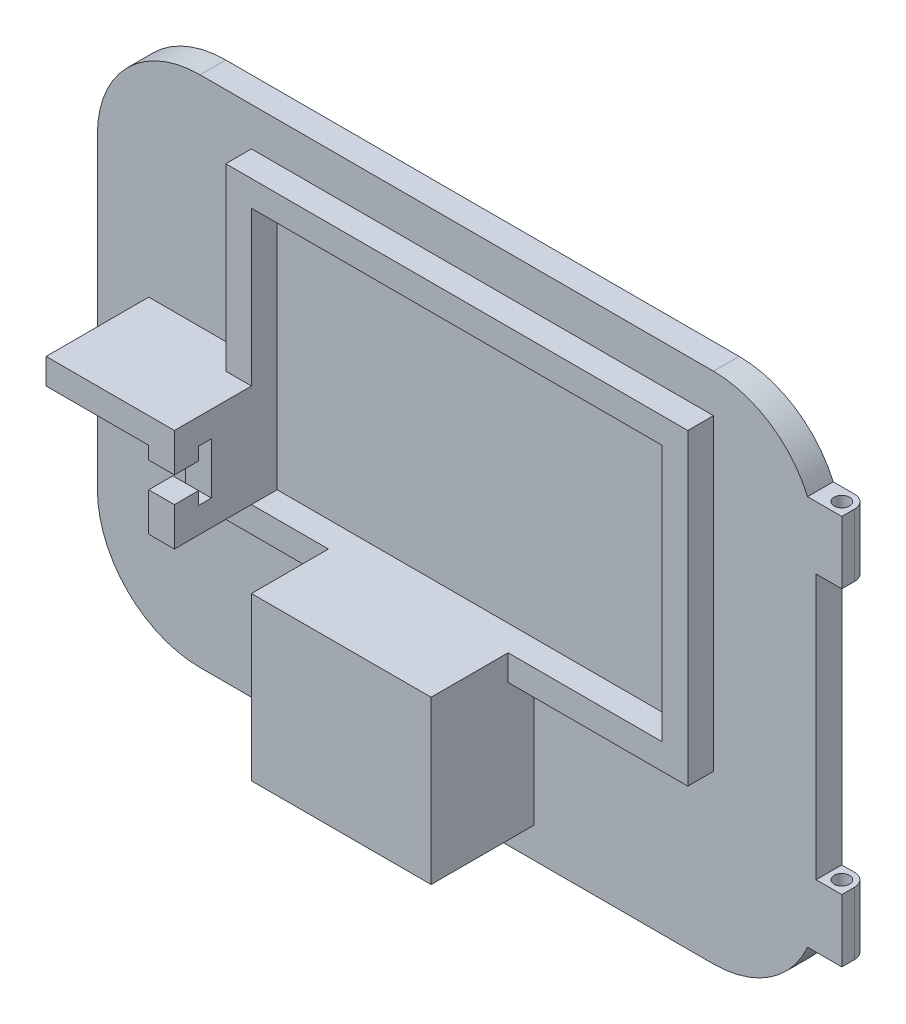
SolidWorks part; units mm, degrees
ref_plane "Front Plane" through (0, 0, 0) normal (0, 0, 1) x (1, 0, 0)
ref_plane "Top Plane" through (0, 0, 0) normal (0, 1, 0) x (1, 0, 0)
ref_plane "Right Plane" through (0, 0, 0) normal (1, 0, 0) x (0, 0, -1)
sketch "Sketch1" plane through (0, 0, 0) normal (0, 0, 1) x (1, 0, 0)
  line L0 (-63.5, 63.5) -> (63.5, 63.5)
  line L1 (63.5, -63.5) -> (-63.5, -63.5)
  line L2 (-88.9, -38.1) -> (-88.9, 38.1)
  line L3 (88.9, -38.1) -> (88.9, 38.1)
  arc A0 (-88.9, 38.1) -> (-63.5, 63.5) centre (-63.5, 38.1) cw
  arc A1 (-63.5, -63.5) -> (-88.9, -38.1) centre (-63.5, -38.1) cw
  arc A2 (63.5, -63.5) -> (88.9, -38.1) centre (63.5, -38.1) ccw
  arc A3 (88.9, 38.1) -> (63.5, 63.5) centre (63.5, 38.1) ccw
  dimension "D1" = 25.4
  dimension "D2" = 88.9
  dimension "D3" = 88.9
  dimension "D4" = 63.5
  dimension "D5" = 63.5
extrude "Boss-Extrude1" add sketch "Sketch1" against normal blind 6.35
sketch "Sketch3" plane through (0, 0, 0) normal (0, 0, 1) x (1, 0, 0)
  line L0 (63.5, 63.5) -> (88.9, 63.5) construction
  line L1 (88.9, 63.5) -> (95.25, 63.5) construction
  line L6 (95.25, 32.75) -> (95.25, 48.26)
  line L8 (95.25, 48.26) -> (86.7795, 48.26)
  line L9 (95.25, 63.5) -> (95.25, 32.75) construction
  line L10 (95.25, 32.75) -> (88.9, 32.75)
  line L11 (88.9, -38.1) -> (88.9, 38.1) construction
  line L12 (88.9, 32.75) -> (88.9, 38.1)
  arc A0 (88.9, 38.1) -> (86.7795, 48.26) centre (63.5, 38.1) ccw
  dimension "D5" = 25.4
  dimension "D1" = 25.4
  dimension "D2" = 6.35
  dimension "D3" = 30.75
  dimension "D4" = 15.24
extrude "Boss-Extrude2" add sketch "Sketch3" against normal up to surface (6.35 mm away) up to face at (0, 0, -6.35)
sketch "Sketch4" plane through (0, 48.26, 0) normal (0, 1, 0) x (1, 0, 0)
  line L0 (95.25, 3.175) -> (92.075, 3.175) construction
  line L1 (95.25, 6.35) -> (95.25, 0) construction
  circle A0 centre (92.075, 3.175) radius 1.905
  point P6 (93.98, 3.175)
  dimension "D1" = 3.81
  dimension "D2" = 1.27
extrude "Cut-Extrude2" cut sketch "Sketch4" against normal up to next
sketch "Sketch5" plane through (0, 0, 0) normal (0, 0, 1) x (1, 0, 0)
  line L0 (0, 0) -> (88.9402, 0)
mirror "Mirror1" about plane through (0, 0, 0) normal (0, 1, 0) of "Cut-Extrude2", "Boss-Extrude2"
sketch "Sketch7" plane through (0, 0, -6.35) normal (0, 0, -1) x (-1, 0, 0)
  line L0 (0, 0) -> (57.15, 0) construction
  point P4 (57.15, 0)
  dimension "D1" = 57.15
ref_plane "Plane1" through (-57.15, 0, -6.35) normal (-1, 0, 0) x (0, 0, 1)
sketch "Sketch8" plane through (-57.15, 0, -6.35) normal (-1, 0, 0) x (0, 0, 1)
  line L0 (0, 0) -> (0, 38.1) construction
  line L1 (0, 38.1) -> (0, 44.45)
  line L2 (-19.05, 25.4) -> (-19.05, -25.4)
  line L3 (0, 24.7494) -> (-24.0575, 24.7494) construction
  line L4 (-12.7, 25.4) -> (-12.7, 40.5526) construction
  line L5 (-19.05, 0) -> (-12.7, 0) construction
  line L6 (-12.7, -25.4) -> (-12.7, 25.4)
  line L7 (0, -38.1) -> (0, -44.45)
  arc A0 (0, 44.45) -> (-19.05, 25.4) centre (0, 25.4) ccw
  arc A1 (0, 38.1) -> (-12.7, 25.4) centre (0, 25.4) ccw
  arc A2 (0, -38.1) -> (-12.7, -25.4) centre (0, -25.4) cw
  arc A3 (0, -44.45) -> (-19.05, -25.4) centre (0, -25.4) cw
  dimension "D1" = 38.1
  dimension "D2" = 6.35
  dimension "D3" = 19.7006
  dimension "D4" = 12.7
extrude "Boss-Extrude3" add sketch "Sketch8" against normal blind 12.7
fillet "Fillet1" radius 6.35 1 edges at (-50.8, -44.45, -6.35)
fillet "Fillet2" radius 6.35 1 edges at (-57.15, -44.0467, -6.35)
fillet "Fillet3" radius 6.35 1 edges at (-44.45, -44.0467, -6.35)
fillet "Fillet4" radius 6.35 3 edges at (-50.8, 44.45, -6.35) (-44.45, 41.275, -6.35) (-57.15, 41.275, -6.35)
fillet "Fillet5" radius 3.175 2 edges at (95.25, -40.505, -6.35) (95.25, 40.505, -6.35)
sketch "Sketch9" plane through (0, 0, 0) normal (0, 0, 1) x (1, 0, 0)
  line L0 (88.9402, 0) -> (-88.9, 0) construction
  line L1 (-88.9, 38.1) -> (-88.9, -38.1) construction
  line L22 (57.15, 47.625) -> (-44.45, 47.625)
  line L23 (57.15, 47.625) -> (57.15, -15.875)
  line L24 (57.15, -15.875) -> (-44.45, -15.875)
  line L25 (-44.45, 47.625) -> (-44.45, -15.875)
  line L26 (-63.5, -63.5) -> (63.5, -63.5) construction
  line L28 (63.5, 53.975) -> (63.5, -22.225)
  line L29 (63.5, -22.225) -> (-50.8, -22.225)
  line L30 (-50.8, 53.975) -> (-50.8, -22.225)
  line L31 (63.5, 53.975) -> (-50.8, 53.975)
  dimension "D1" = 63.5
  dimension "D2" = 101.6
  dimension "D3" = 47.625
  dimension "D4" = 38.1
  dimension "D5" = 6.35
extrude "Boss-Extrude4" add sketch "Sketch9" along normal blind 6.35
sketch "Sketch10" plane through (0, 0, 0) normal (0, 0, 1) x (1, 0, 0)
  line L0 (-44.45, 47.625) -> (-44.45, 10.9459) construction
  line L1 (57.15, -15.875) -> (57.15, -25.527) construction
  line L2 (32.639, -25.527) -> (51.689, -25.527) construction
  line L3 (32.639, -23.9395) -> (51.689, -23.9395)
  line L4 (32.639, -27.1145) -> (51.689, -27.1145)
  line L5 (57.15, -25.527) -> (42.164, -25.527) construction
  arc A0 (32.639, -23.9395) -> (32.639, -27.1145) centre (32.639, -25.527) ccw
  arc A1 (51.689, -27.1145) -> (51.689, -23.9395) centre (51.689, -25.527) ccw
  point P6 (42.164, -25.527)
  point P11 (0, 0)
  dimension "D1" = 9.652
  dimension "D2" = 14.986
  dimension "D3" = 19.05
  dimension "D4" = 3.175
extrude "Cut-Extrude3" cut sketch "Sketch10" against normal up to next
sketch "Sketch14" plane through (0, 0, 0) normal (0, 0, 1) x (1, 0, 0)
  line L0 (12.7, -22.225) -> (12.7, -49.657)
  line L1 (-50.8, -22.225) -> (63.5, -22.225) construction
  line L2 (12.7, -49.657) -> (-25.4, -49.657)
  line L3 (63.5, -22.225) -> (63.5, 53.975) construction
  line L4 (19.05, -22.225) -> (19.05, -56.007)
  line L5 (19.05, -56.007) -> (-25.4, -56.007)
  line L6 (-25.4, -56.007) -> (-25.4, -49.657)
  line L7 (19.05, -15.875) -> (-25.4, -15.875)
  line L8 (-44.45, -15.875) -> (57.15, -15.875) construction
  line L9 (-25.4, -15.875) -> (-25.4, -22.225)
  line L10 (-25.4, -22.225) -> (12.7, -22.225)
  line L11 (19.05, -22.225) -> (19.05, -15.875)
  dimension "D1" = 38.1
  dimension "D2" = 27.432
  dimension "D3" = 50.8
  dimension "D4" = 6.35
extrude "Boss-Extrude7" add sketch "Sketch14" along normal blind 25.4
sketch "Sketch15" plane through (0, -49.657, 0) normal (0, 1, 0) x (1, 0, 0)
  line L0 (-25.4, -25.4) -> (-25.4, -19.05)
  line L1 (-25.4, -25.4) -> (-25.4, 0) construction
  line L2 (-25.4, -19.05) -> (12.7, -19.05)
  line L3 (12.7, -25.4) -> (12.7, 0) construction
  line L4 (12.7, -19.05) -> (12.7, -25.4)
  line L5 (12.7, -25.4) -> (-25.4, -25.4)
  dimension "D1" = 6.35
extrude "Boss-Extrude8" add sketch "Sketch15" along normal up to next
sketch "Sketch16" plane through (0, 0, 0) normal (0, 0, 1) x (1, 0, 0)
  line L0 (-50.8, 3.175) -> (-76.2, 3.175)
  line L1 (-50.8, 53.975) -> (-50.8, -22.225) construction
  line L2 (63.5, 53.975) -> (-50.8, 53.975) construction
  line L3 (-76.2, 9.525) -> (-76.2, 3.175)
  line L4 (-50.8, 9.525) -> (-44.45, 9.525)
  line L5 (-44.45, 47.625) -> (-44.45, -15.875) construction
  line L6 (-44.45, 9.525) -> (-44.45, -15.875)
  line L7 (-44.45, -15.875) -> (-50.8, -15.875)
  line L8 (-50.8, -15.875) -> (-50.8, 3.175)
  line L9 (-44.45, -15.875) -> (-25.4, -15.875) construction
  line L13 (-50.8, 9.525) -> (-76.2, 9.525)
  point P8 (-47.625, -15.875)
  dimension "D1" = 25.4
  dimension "D2" = 50.8
  dimension "D3" = 6.35
extrude "Boss-Extrude9" add sketch "Sketch16" along normal blind 25.4
sketch "Sketch17" plane through (-50.8, 0, 0) normal (-1, 0, 0) x (0, 0, 1)
  line L0 (0, 3.175) -> (16.256, 3.175) construction
  line L1 (0, 3.175) -> (25.4, 3.175) construction
  line L2 (16.256, 3.175) -> (16.256, -9.525)
  line L3 (16.256, -9.525) -> (19.431, -9.525)
  line L4 (19.431, -9.525) -> (19.431, 3.175)
  line L5 (19.431, 3.175) -> (16.256, 3.175)
  dimension "D1" = 16.256
  dimension "D2" = 12.7
  dimension "D3" = 3.175
extrude "Cut-Extrude4" cut sketch "Sketch17" against normal up to next
sketch "Sketch18" plane through (0, 0, 25.4) normal (0, 0, 1) x (1, 0, 0)
  line L0 (-50.8, 0) -> (-44.45, 0) construction
  line L1 (-44.45, -15.875) -> (-44.45, 9.525) construction
  line L4 (-50.8, 3.175) -> (-50.8, -15.875) construction
  line L5 (-44.45, 0) -> (-50.8, 0)
  line L6 (-44.45, 0) -> (-44.45, -6.35)
  line L7 (-44.45, -6.35) -> (-50.8, -6.35)
  line L8 (-50.8, 0) -> (-50.8, -6.35)
  line L9 (-44.45, 0) -> (-50.8, -6.35) construction
  line L10 (-44.45, -6.35) -> (-50.8, 0) construction
  line L11 (-44.45, 47.625) -> (-44.45, -15.875) construction
  line L12 (-76.2, 3.175) -> (-50.8, 3.175) construction
  dimension "D1" = 6.35
  dimension "D2" = 3.175
extrude "Cut-Extrude5" cut sketch "Sketch18" against normal up to next
